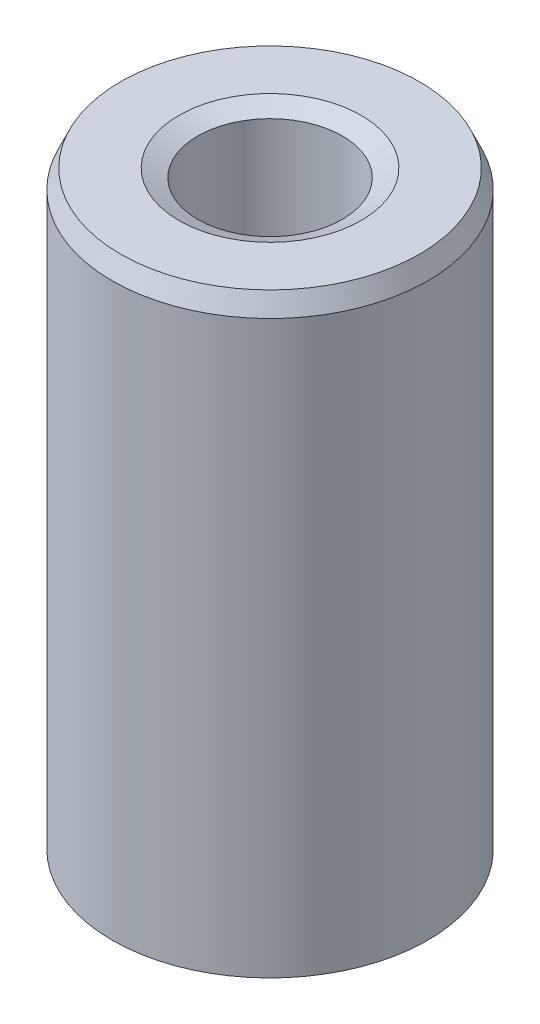
SolidWorks part; units mm, degrees
ref_plane "Front Plane" through (0, 0, 0) normal (0, 0, 1) x (1, 0, 0)
ref_plane "Top Plane" through (0, 0, 0) normal (0, 1, 0) x (1, 0, 0)
ref_plane "Right Plane" through (0, 0, 0) normal (1, 0, 0) x (0, 0, -1)
sketch "Sketch1" plane through (0, 0, 0) normal (0, 1, 0) x (1, 0, 0)
  circle A0 centre (0, 0) radius 12.5
  dimension "SLEEVE_OD" = 25
extrude "Boss-Extrude1" add sketch "Sketch1" along normal blind 47.3826
sketch "Sketch2" plane through (0, 0, 0) normal (0, 1, 0) x (1, 0, 0)
  circle A0 centre (0, 0) radius 5.7262
  dimension "BORE_D" = 11.4525
extrude "Cut-Extrude1" cut sketch "Sketch2" along normal through all
chamfer "Chamfer1" distance 1.4907 angle 24.1 4 edges at (0, 47.3826, 5.7262) (0, 0, 5.7262) (0, 0, 12.5) (0, 47.3826, 12.5) first distance on face at (0, 47.3826, 5.7262) first distance on face at (0, 0, 5.7262) first distance on face at (0, 47.3826, 12.5)
